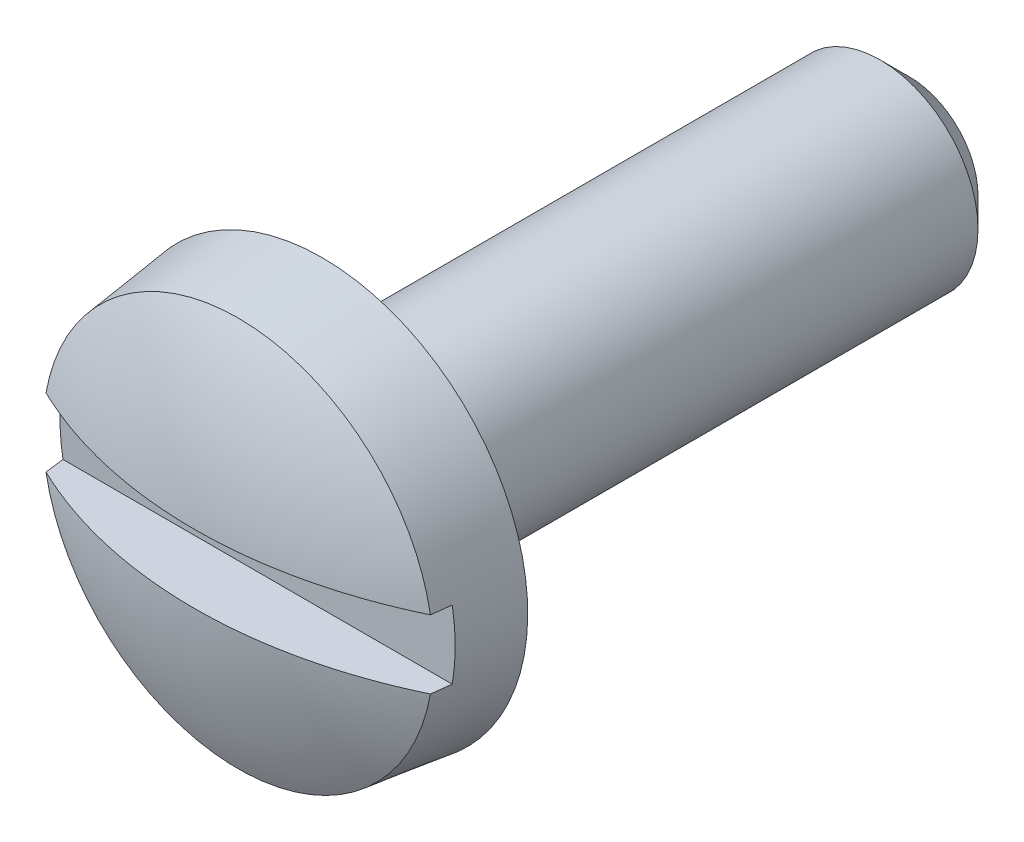
SolidWorks part; units mm, degrees
material "AISI 304"
ref_plane "Front" through (0, 0, 0) normal (0, 0, 1) x (1, 0, 0)
ref_plane "Top" through (0, 0, 0) normal (0, 1, 0) x (1, 0, 0)
ref_plane "Right" through (0, 0, 0) normal (1, 0, 0) x (0, 0, -1)
sketch "Sketch1" plane through (0, 0, 0) normal (0, 0, 1) x (1, 0, 0)
  circle A0 centre (0, 0) radius 6.6675
  dimension "Head Dia" = 13.335
extrude "Extrude3" add sketch "Sketch1" along normal blind 4.191
sketch "Sketch11" plane through (0, 0, 0) normal (1, 0, 0) x (0, 0, -1)
  line L0 (0, 0) -> (-4.445, 0) construction
  line L3 (0, 6.6675) -> (-4.191, 6.6675) construction
  line L4 (-4.191, 6.6675) -> (-4.191, -6.6675) construction
  line L5 (-4.445, 6.9342) -> (0, 6.9342)
  line L7 (0, 6.9342) -> (0, 6.6675)
  line L8 (-2.7242, 6.333) -> (0, 6.6675)
  line L9 (0, -6.6675) -> (0, 6.6675) construction
  line L13 (-4.191, 0) -> (-4.445, 0)
  line L14 (-4.445, 0) -> (-4.445, 6.9342)
  arc A0 (-2.7242, 6.333) -> (-4.191, 0) centre (10.2136, 0) ccw
  dimension "D3" = 0.254
  dimension "D5" = 0.2667
  dimension "D1" = 7
  dimension "D2" = 1.4668
revolve "Cut-Revolve3" cut sketch "Sketch11" angle 360 about L0
sketch "Sketch4" plane through (0, 0, 0) normal (1, 0, 0) x (0, 0, -1)
  line L0 (0, 0) -> (19.05, 0)
  line L3 (19.05, 0) -> (19.05, 3.175)
  line L4 (19.05, 3.175) -> (0, 3.175)
  line L6 (0, 3.175) -> (0, 0)
  line L9 (19.05, 3.175) -> (19.05, -3.175) construction
  dimension "length" = 19.05
  dimension "dia" = 6.35
revolve "Revolve1" add sketch "Sketch4" angle 360 about L0
sketch "Sketch13" plane through (0, 0, -19.05) normal (0, 0, -1) x (-1, 0, 0)
  circle A2 centre (0, 0) radius 3.175
curve "Helix/Spiral1" pitch 1.27 height 19.05 turns 15
chamfer "Chamfer2" distance 0.9525 angle 45 1 edges at (3.175, 0, -19.05)
sketch "Sketch14" plane through (0, 0, 0) normal (1, 0, 0) x (0, 0, -1)
  line L0 (19.05, 3.2147) -> (20.1612, 3.2147)
  line L1 (20.1612, 3.2147) -> (19.685, 2.3555)
  line L2 (19.685, 2.3555) -> (19.5262, 2.3555)
  line L3 (19.5262, 2.3555) -> (19.05, 3.2147)
  line L4 (19.2881, 2.7851) -> (19.9231, 2.7851) construction
  dimension "D1" = 0.1588
  dimension "D2" = 58
  dimension "D3" = 0.635
  dimension "D4" = 0.0397
sweep "Cut-Sweep1" [suppressed] cut profiles "Sketch14" path "Helix/Spiral1"
ref_plane "Plane1" through (0, 0, 19.05) normal (0, 0, -1) x (-1, 0, 0)
sketch "Sketch29" [suppressed] plane through (0, 0, 19.05) normal (0, 0, -1) x (-1, 0, 0)
  circle A0 centre (0, 0) radius 3.175 construction
  circle A1 centre (0, 0) radius 3.175
  point P3 (0, -3.175)
  point P4 (0, 3.175)
extrude "Extrude11" [suppressed] add sketch "Sketch29" against normal up to surface (19.05 mm away) up to plane "Front"
ref_plane "Plane2" through (0, 0, 4.191) normal (0, 0, 1) x (1, 0, 0)
sketch "Sketch26" plane through (0, 0, 0) normal (0, 0, 1) x (1, 0, 0)
  circle A1 centre (0, 0) radius 0.5461
  dimension "D1" = 1.0922
extrude "Extrude13" [suppressed] add sketch "Sketch26" along normal up to surface (4.1806 mm away)
sketch "Sketch31" plane through (0, 0, 4.191) normal (0, 0, 1) x (1, 0, 0)
  line L0 (-6.6675, 1.1112) -> (6.6675, -1.1112) construction
  line L1 (-6.6675, 1.1112) -> (6.6675, 1.1113)
  line L2 (-6.6675, 1.1112) -> (-6.6675, -1.1113)
  line L3 (-6.6675, -1.1113) -> (6.6675, -1.1112)
  line L4 (6.6675, 1.1113) -> (6.6675, -1.1112)
  circle A0 centre (0, 0) radius 6.6675 construction
  dimension "D1" = 2.2225
extrude "Extrude15" cut sketch "Sketch31" against normal blind 2.0955
sketch "Sketch18" plane through (0, 0, 0) normal (1, 0, 0) x (0, 0, -1)
  line L1 (19.05, 3.175) -> (0, 3.175) construction
  point P0 (17.145, -3.175)
  point P1 (17.78, 3.175)
  point P2 (-4.191, 1.1113)
  dimension "D1" = 1.27
  dimension "D2" = 1.905
other "DeleteFace1" [suppressed]
equation "\"D3@Helix/Spiral1\" = \"length@Sketch4\""
equation "\"D1@Sketch14\" = \"D4@Helix/Spiral1\" * .125"
equation "\"D3@Sketch14\" = \"D4@Helix/Spiral1\" * .5"
equation "\"D5@Sketch11\" = \"Head Dia@Sketch1\" * .02"
equation "\"D4@Sketch14\" = \"D1@Sketch14\" * .25"
equation "\"D1@Chamfer2\" = \"D4@Helix/Spiral1\" * .75"
equation "\"D1@Sketch18\" = \"D4@Helix/Spiral1\""
equation "\"D2@Sketch18\" = \"D4@Helix/Spiral1\" * 1.5"
equation "\"D1@Extrude15\" = \"Head Ht@Extrude3\" * .5"
equation "\"D2@Sketch11\" = \"Head Ht@Extrude3\" * .35"
equation "\"D1@Sketch31\" = \"D4@Helix/Spiral1\" * 1.75"
